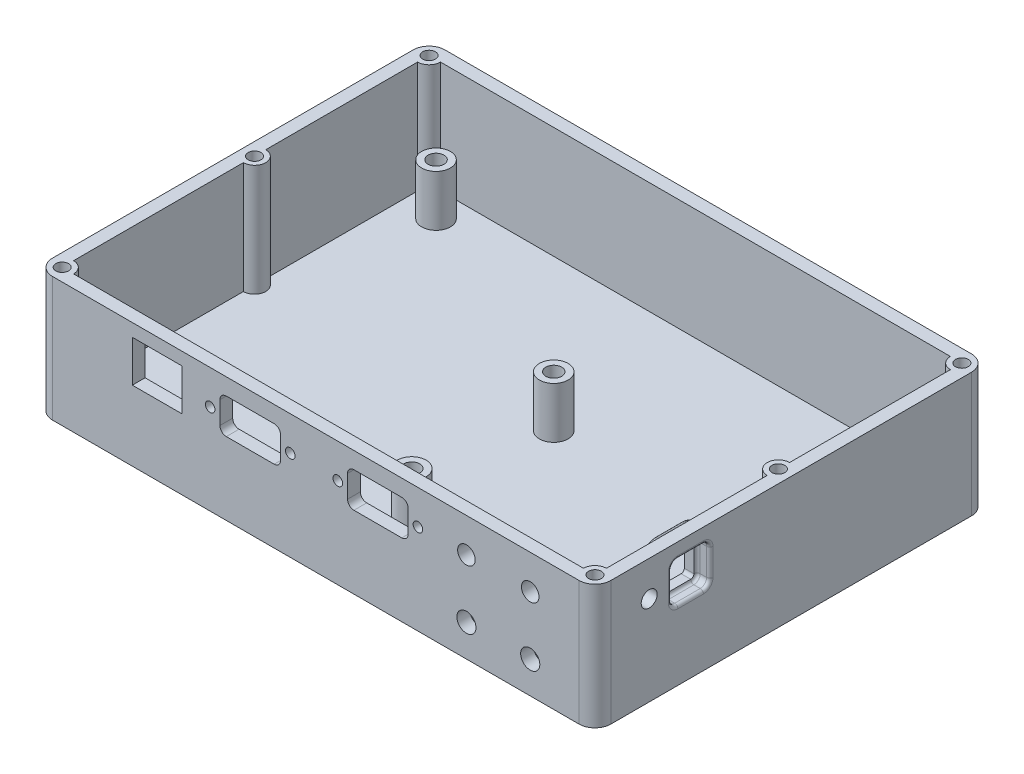
SolidWorks part; units mm, degrees
ref_plane "Ön Düzlem" through (0, 0, 0) normal (0, 0, 1) x (1, 0, 0)
ref_plane "Üst Düzlem" through (0, 0, 0) normal (0, 1, 0) x (1, 0, 0)
ref_plane "Sağ Düzlem" through (0, 0, 0) normal (1, 0, 0) x (0, 0, -1)
sketch "Çizim1" plane through (0, 0, 0) normal (0, 1, 0) x (1, 0, 0)
  line L0 (-87.5, 61.5) -> (87.5, -61.5) construction
  line L1 (-87.5, -61.5) -> (87.5, -61.5)
  line L2 (-87.5, -61.5) -> (-87.5, 61.5)
  line L3 (-87.5, 61.5) -> (87.5, 61.5)
  line L4 (87.5, -61.5) -> (87.5, 61.5)
  dimension "D1" = 123
  dimension "D2" = 175
extrude "Yükseklik-Ekstrüzyon1" add sketch "Çizim1" along normal blind 4
sketch "Çizim2" plane through (0, 4, 0) normal (0, 1, 0) x (1, 0, 0)
  line L0 (-83.5, 57.5) -> (-83.5, -57.5)
  line L1 (-87.5, 61.5) -> (87.5, 61.5)
  line L2 (-87.5, 61.5) -> (-87.5, -61.5)
  line L3 (-87.5, -61.5) -> (87.5, -61.5)
  line L4 (87.5, 61.5) -> (87.5, -61.5)
  line L5 (-83.5, -57.5) -> (83.5, -57.5)
  line L6 (83.5, 57.5) -> (83.5, -57.5)
  line L7 (-83.5, 57.5) -> (83.5, 57.5)
  dimension "D1" = 4
extrude "Yükseklik-Ekstrüzyon2" add sketch "Çizim2" along normal blind 35
sketch "Çizim3" plane through (0, 0, 61.5) normal (0, 0, 1) x (1, 0, 0)
  line L0 (-87.5, 0) -> (87.5, 0) construction
  line L1 (-57.5, 35) -> (-42, 35)
  line L2 (-57.5, 35) -> (-57.5, 22)
  line L3 (-57.5, 22) -> (-42, 22)
  line L4 (-42, 35) -> (-42, 22)
  line L5 (-28.045, 33.7748) -> (-13.045, 33.7748)
  line L6 (-30.045, 31.7748) -> (-30.045, 24.7748)
  line L7 (-28.045, 22.7748) -> (-13.045, 22.7748)
  line L8 (-11.045, 31.7748) -> (-11.045, 24.7748)
  line L9 (11.96, 33.7748) -> (26.96, 33.7748)
  line L10 (9.96, 31.7748) -> (9.96, 24.7748)
  line L11 (11.96, 22.7748) -> (26.96, 22.7748)
  line L12 (28.96, 31.7748) -> (28.96, 24.7748)
  circle A0 centre (-33.1, 28.2748) radius 1.5
  circle A1 centre (-7.99, 28.2748) radius 1.5
  circle A2 centre (6.9, 28.2748) radius 1.5
  circle A3 centre (32.01, 28.2748) radius 1.5
  arc A4 (26.96, 22.7748) -> (28.96, 24.7748) centre (26.96, 24.7748) ccw
  circle A5 centre (47.2121, 28.2748) radius 2.75
  circle A6 centre (67.2121, 28.2748) radius 2.75
  arc A7 (9.96, 24.7748) -> (11.96, 22.7748) centre (11.96, 24.7748) ccw
  arc A8 (11.96, 33.7748) -> (9.96, 31.7748) centre (11.96, 31.7748) ccw
  arc A9 (26.96, 33.7748) -> (28.96, 31.7748) centre (26.96, 31.7748) cw
  arc A10 (-13.045, 22.7748) -> (-11.045, 24.7748) centre (-13.045, 24.7748) ccw
  arc A11 (-30.045, 24.7748) -> (-28.045, 22.7748) centre (-28.045, 24.7748) ccw
  arc A12 (-28.045, 33.7748) -> (-30.045, 31.7748) centre (-28.045, 31.7748) ccw
  arc A13 (-13.045, 33.7748) -> (-11.045, 31.7748) centre (-13.045, 31.7748) cw
  circle A14 centre (47.2121, 10) radius 3
  circle A15 centre (67.2121, 10) radius 3
  point P27 (28.96, 22.7748)
  point P32 (9.96, 33.7748)
  point P35 (28.96, 33.7748)
  point P38 (-11.045, 22.7748)
  point P43 (-30.045, 33.7748)
  point P46 (-11.045, 33.7748)
  dimension "D3" = 25.11
  dimension "D8" = 20
  dimension "D9" = 3
  dimension "D10" = 5.5
  dimension "D11" = 19
  dimension "D19" = 2
  dimension "D20" = 20
  dimension "D1" = 13
  dimension "D2" = 15.5
  dimension "D4" = 25.11
  dimension "D5" = 14.89
  dimension "D6" = 8.9
  dimension "D7" = 26
  dimension "D12" = 11
  dimension "D13" = 5.5
  dimension "D14" = 3.055
  dimension "D15" = 19
  dimension "D16" = 11
  dimension "D17" = 3.06
  dimension "D18" = 5.5
  dimension "D21" = 10
  dimension "D22" = 6.2748
  dimension "D23" = 22
extrude "Kes-Ekstrüzyon1" cut sketch "Çizim3" against normal blind 10
sketch "Çizim4" plane through (0, 0, 57.5) normal (0, 0, -1) x (-1, 0, 0)
  line L0 (83.5, 4) -> (-83.5, 4) construction
  line L1 (-80.9453, 36.5) -> (78.2977, 36.5)
  line L2 (-80.9453, 36.5) -> (-80.9453, 4)
  line L3 (-80.9453, 4) -> (78.2977, 4)
  line L4 (78.2977, 36.5) -> (78.2977, 4)
  line L5 (83.5, 39) -> (-83.5, 39) construction
  dimension "D1" = 2.5
extrude "Kes-Ekstrüzyon2" [suppressed] cut sketch "Çizim4" against normal blind 2
sketch "Çizim5" plane through (87.5, 0, 0) normal (1, 0, 0) x (0, 0, -1)
  line L0 (-61.5, 0) -> (61.5, 0) construction
  line L1 (-31.5, 28) -> (-31.5, 21.81) construction
  line L2 (-35.5, 21.81) -> (-27.5, 21.81)
  line L3 (-37.5, 23.81) -> (-37.5, 32.2462)
  line L4 (-35.5, 34.2462) -> (-27.5, 34.2462)
  line L5 (-25.5, 23.81) -> (-25.5, 32.2462)
  circle A1 centre (-44.5, 28) radius 2.5
  arc A2 (-35.5, 21.81) -> (-37.5, 23.81) centre (-35.5, 23.81) cw
  arc A3 (-27.5, 21.81) -> (-25.5, 23.81) centre (-27.5, 23.81) ccw
  arc A4 (-27.5, 34.2462) -> (-25.5, 32.2462) centre (-27.5, 32.2462) cw
  arc A5 (-37.5, 32.2462) -> (-35.5, 34.2462) centre (-35.5, 32.2462) cw
  dimension "D1" = 26
  dimension "D2" = 13
  dimension "D4" = 2
  dimension "D3" = 28
  dimension "D5" = 12
extrude "Kes-Ekstrüzyon3" cut sketch "Çizim5" against normal blind 5
fillet "Radyus1" radius 5 4 edges at (-87.5, 19.5, 61.5) (-87.5, 19.5, -61.5) (87.5, 19.5, -61.5) (87.5, 19.5, 61.5)
sketch "Çizim6" plane through (0, 4, 0) normal (0, 1, 0) x (1, 0, 0)
  line L2 (-83.5, -54.3723) -> (-83.5, -51.8818)
  line L5 (-83.5, 57.5) -> (-83.5, -57.5) construction
  line L6 (-75.2834, -57.5) -> (-73.2805, -57.5)
  line L7 (-83.5, -57.5) -> (83.5, -57.5) construction
  circle A0 centre (-73.105, 49.29) radius 2.5
  circle A1 centre (2.895, 10.19) radius 2.5
  circle A2 centre (6.895, -38.31) radius 2.5
  arc A3 (-75.2834, -57.5) -> (-83.5, -54.3723) centre (-80.105, -57.81) ccw
  circle A4 centre (77.395, -55.31) radius 2.5
  circle A5 centre (77.395, -55.31) radius 4.5
  circle A6 centre (76.895, 49.19) radius 2.5
  circle A7 centre (-73.105, 49.29) radius 4.5
  circle A8 centre (76.895, 49.19) radius 4.5
  circle A9 centre (2.895, 10.19) radius 4.5
  circle A10 centre (6.895, -38.31) radius 4.5
  arc A11 (-73.2805, -57.5) -> (-83.5, -51.8818) centre (-80.105, -57.81) ccw
  circle A12 centre (-80.105, -57.81) radius 6.8316 construction
  circle A13 centre (-80.105, -57.81) radius 4.8316 construction
  dimension "D2" = 2
  dimension "D10" = 2
extrude "Yükseklik-Ekstrüzyon3" add sketch "Çizim6" along normal blind 16
sketch "Çizim7" plane through (0, 39, 0) normal (0, 1, 0) x (1, 0, 0)
  line L0 (-83.5, 57.5) -> (-83.5, -51.8818) construction
  line L1 (83.5, -57.5) -> (83.5, 57.5) construction
  circle A0 centre (-83.5, 57.5) radius 2
  circle A1 centre (83.5, 57.5) radius 2
  circle A2 centre (83.5, -57.5) radius 2
  circle A3 centre (-83.5, -57.5) radius 2
  circle A4 centre (-83.5, 2.8091) radius 2
  circle A5 centre (83.5, 0) radius 2
extrude "Kes-Ekstrüzyon4" cut sketch "Çizim7" against normal blind 15
sketch "Çizim8" plane through (0, 39, 0) normal (0, 1, 0) x (1, 0, 0)
  line L0 (83.5, -57.5) -> (83.5, 57.5) construction
  line L1 (-83.5, 4.8091) -> (-83.5, 0.8091) construction
  circle A0 centre (-83.5, 57.5) radius 3.5858
  circle A1 centre (-83.5, -57.5) radius 3.5858
  circle A2 centre (83.5, -57.5) radius 3.5858
  circle A3 centre (83.5, 0) radius 3.5
  circle A4 centre (-83.5, 2.8091) radius 3.5
  circle A5 centre (-83.5, 2.8091) radius 2
  circle A6 centre (-83.5, 57.5) radius 2
  circle A7 centre (83.5, 57.5) radius 2
  circle A8 centre (83.5, 57.5) radius 3.5858
  circle A9 centre (83.5, 0) radius 2
  circle A10 centre (83.5, -57.5) radius 2
  circle A11 centre (-83.5, -57.5) radius 2
extrude "Yükseklik-Ekstrüzyon4" add sketch "Çizim8" against normal up to next
sketch "Çizim9" plane through (83.5, 0, 0) normal (-1, 0, 0) x (0, 0, 1)
  line L20 (22.5, 32.2462) -> (22.5, 23.81)
  line L21 (27.5, 18.81) -> (35.5, 18.81)
  line L22 (40.5, 23.81) -> (40.5, 32.2462)
  line L23 (35.5, 37.2462) -> (27.5, 37.2462)
  line L28 (36.5, 23.81) -> (36.5, 32.2462)
  line L29 (27.5, 22.81) -> (35.5, 22.81)
  line L30 (26.5, 32.2462) -> (26.5, 23.81)
  line L31 (35.5, 33.2462) -> (27.5, 33.2462)
  line L32 (36.5, 23.81) -> (36.5, 32.2462)
  line L33 (27.5, 22.81) -> (35.5, 22.81)
  line L34 (26.5, 32.2462) -> (26.5, 23.81)
  line L35 (35.5, 33.2462) -> (27.5, 33.2462)
  arc A16 (22.5, 23.81) -> (27.5, 18.81) centre (27.5, 23.81) ccw
  arc A17 (35.5, 18.81) -> (40.5, 23.81) centre (35.5, 23.81) ccw
  arc A18 (40.5, 32.2462) -> (35.5, 37.2462) centre (35.5, 32.2462) ccw
  arc A19 (27.5, 37.2462) -> (22.5, 32.2462) centre (27.5, 32.2462) ccw
  arc A24 (36.5, 32.2462) -> (35.5, 33.2462) centre (35.5, 32.2462) ccw
  arc A25 (35.5, 22.81) -> (36.5, 23.81) centre (35.5, 23.81) ccw
  arc A26 (26.5, 23.81) -> (27.5, 22.81) centre (27.5, 23.81) ccw
  arc A27 (27.5, 33.2462) -> (26.5, 32.2462) centre (27.5, 32.2462) ccw
  arc A28 (36.5, 32.2462) -> (35.5, 33.2462) centre (35.5, 32.2462) ccw
  arc A29 (35.5, 22.81) -> (36.5, 23.81) centre (35.5, 23.81) ccw
  arc A30 (26.5, 23.81) -> (27.5, 22.81) centre (27.5, 23.81) ccw
  arc A31 (27.5, 33.2462) -> (26.5, 32.2462) centre (27.5, 32.2462) ccw
  dimension "D1" = 1
extrude "Yükseklik-Ekstrüzyon5" add sketch "Çizim9" along normal blind 3
fillet "Radyus2" radius 1 8 edges at (83.5, 22.3958, 36.9142) (83.5, 21.81, 31.5) (83.5, 22.3958, 26.0858) (83.5, 28.0281, 25.5) (83.5, 33.6604, 26.0858) (83.5, 34.2462, 31.5) (83.5, 33.6604, 36.9142) (83.5, 28.0281, 37.5)
fillet "Radyus3" radius 1 8 edges at (80.5, 37.2462, 31.5) (80.5, 35.7817, 39.0355) (80.5, 28.0281, 40.5) (80.5, 20.2744, 39.0355) (80.5, 18.81, 31.5) (80.5, 20.2744, 23.9645) (80.5, 28.0281, 22.5) (80.5, 35.7817, 23.9645)
fillet "Radyus4" radius 1 8 edges at (87.5, 33.6604, 36.9142) (87.5, 34.2462, 31.5) (87.5, 33.6604, 26.0858) (87.5, 28.0281, 25.5) (87.5, 22.3958, 26.0858) (87.5, 21.81, 31.5) (87.5, 22.3958, 36.9142) (87.5, 28.0281, 37.5)
